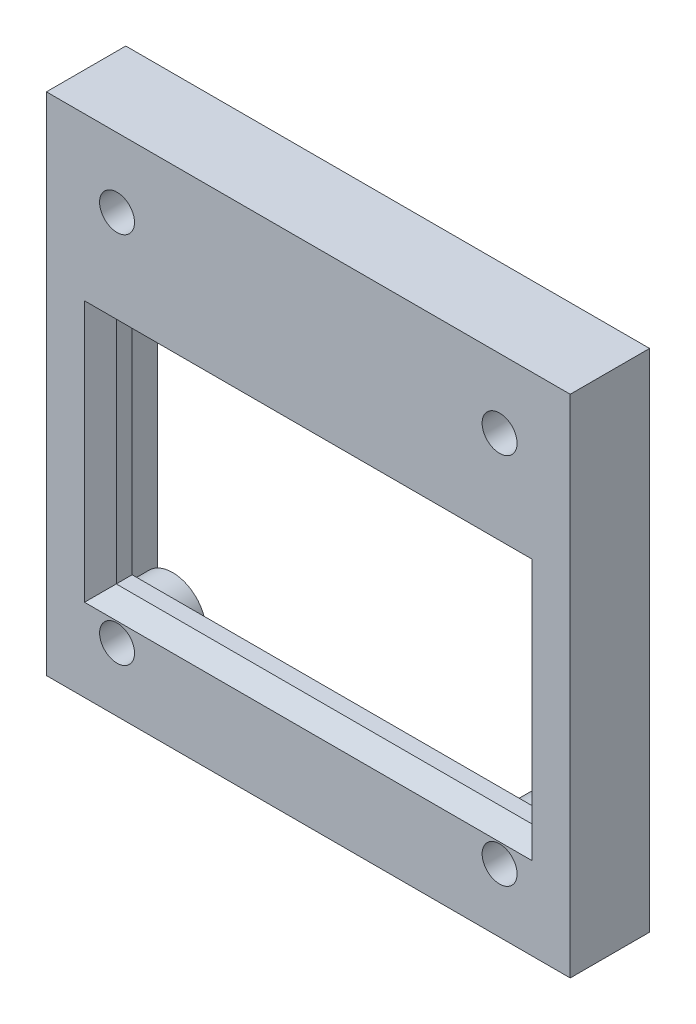
SolidWorks part; units mm, degrees
ref_plane "Front Plane" through (0, 0, 0) normal (0, 0, 1) x (1, 0, 0)
ref_plane "Top Plane" through (0, 0, 0) normal (0, 1, 0) x (1, 0, 0)
ref_plane "Right Plane" through (0, 0, 0) normal (1, 0, 0) x (0, 0, -1)
sketch "Sketch1" plane through (0, 0, 0) normal (0, 0, 1) x (1, 0, 0)
  line L5 (-16.5, -13.425) -> (16.5, -13.425)
  line L6 (-16.5, -13.425) -> (-16.5, 18.425)
  line L7 (13.1, -7.225) -> (-13.1, -7.225)
  line L8 (13.1, -7.225) -> (13.1, 7.225)
  line L9 (13.1, 7.225) -> (-13.1, 7.225)
  line L10 (-13.1, -7.225) -> (-13.1, 7.225)
  line L11 (13.1, -7.225) -> (-13.1, 7.225) construction
  line L12 (13.1, 7.225) -> (-13.1, -7.225) construction
  line L13 (-16.5, 18.425) -> (16.5, 18.425)
  line L14 (16.5, -13.425) -> (16.5, 18.425)
  line L15 (-16.5, -13.425) -> (16.5, 18.425) construction
  line L16 (-16.5, 18.425) -> (16.5, -13.425) construction
  point P0 (0, 0)
  point P1 (0, 2.5)
  point P6 (0, 0)
  dimension "D1" = 26.2
  dimension "D2" = 14.45
  dimension "D3" = 11.2
  dimension "D4" = 6.2
  dimension "D5" = 3.4
  dimension "D6" = 3.4
extrude "Boss-Extrude1" add sketch "Sketch1" along normal blind 2
chamfer "Chamfer1" distance 1 angle 45 4 edges at (13.1, 0, 2) (0, -7.225, 2) (-13.1, 0, 2) (0, 7.225, 2)
sketch "Sketch2" plane through (0, 0, 0) normal (0, 0, -1) x (-1, 0, 0)
  line L1 (-16.5, 18.425) -> (16.5, 18.425)
  line L2 (-16.5, 18.425) -> (-16.5, -13.425)
  line L3 (-16.5, -13.425) -> (16.5, -13.425)
  line L4 (16.5, 18.425) -> (16.5, -13.425)
  line L5 (-14.5, 16.425) -> (14.5, 16.425)
  line L6 (-14.5, 16.425) -> (-14.5, -11.425)
  line L7 (-14.5, -11.425) -> (14.5, -11.425)
  line L8 (14.5, 16.425) -> (14.5, -11.425)
  dimension "D1" = 2
  dimension "D2" = 2
  dimension "D3" = 2
  dimension "D4" = 2
extrude "Boss-Extrude2" add sketch "Sketch2" along normal blind 3
sketch "Sketch3" plane through (0, 0, 0) normal (0, 0, -1) x (-1, 0, 0)
  line L1 (-12.05, 14.075) -> (12.05, 14.075)
  line L2 (-12.05, 14.075) -> (-12.05, -9.425)
  line L3 (-12.05, -9.425) -> (12.05, -9.425)
  line L4 (12.05, 14.075) -> (12.05, -9.425)
  line L5 (-14.5, 16.425) -> (-14.5, -11.425) construction
  line L6 (14.5, 16.425) -> (-14.5, 16.425) construction
  circle A0 centre (-12.05, 14.075) radius 1.1
  circle A1 centre (12.05, 14.075) radius 1.1
  circle A2 centre (12.05, -9.425) radius 1.1
  circle A3 centre (-12.05, -9.425) radius 1.1
  dimension "2.2" = 2.2
  dimension "D1" = 24.1
  dimension "D2" = 23.5
  dimension "D3" = 2.45
  dimension "D4" = 2.35
extrude "Cut-Extrude2" cut sketch "Sketch3" against normal blind 3 contours L1 A0 L2 | L2 A0 L1 | L4 A1 L1 | L1 A1 L4 | L3 A2 L4 | L2 A3 L3 | L3 A3 L2 | A2 region at (12.2056, 14.2306, 0) region at (11.5831, 13.6081, 0) region at (-12.2056, 14.2306, 0) region at (-11.5831, 13.6081, 0) region at (11.5831, -8.9581, 0) region at (12.2056, -9.5806, 0) region at (-12.2056, -9.5806, 0)
sketch "Sketch4" plane through (0, 0, 0) normal (0, 0, -1) x (-1, 0, 0)
  circle A0 centre (-12.05, 14.075) radius 1.1
  circle A1 centre (12.05, 14.075) radius 1.1
  circle A2 centre (-12.05, -9.425) radius 1.1
  circle A3 centre (12.05, -9.425) radius 1.1
  circle A4 centre (-12.05, 14.075) radius 2.1
  circle A5 centre (12.05, 14.075) radius 2.1
  circle A6 centre (-12.05, -9.425) radius 2.1
  circle A7 centre (12.05, -9.425) radius 2.1
  dimension "D1" = 1
extrude "Boss-Extrude3" add sketch "Sketch4" along normal blind 1.5
